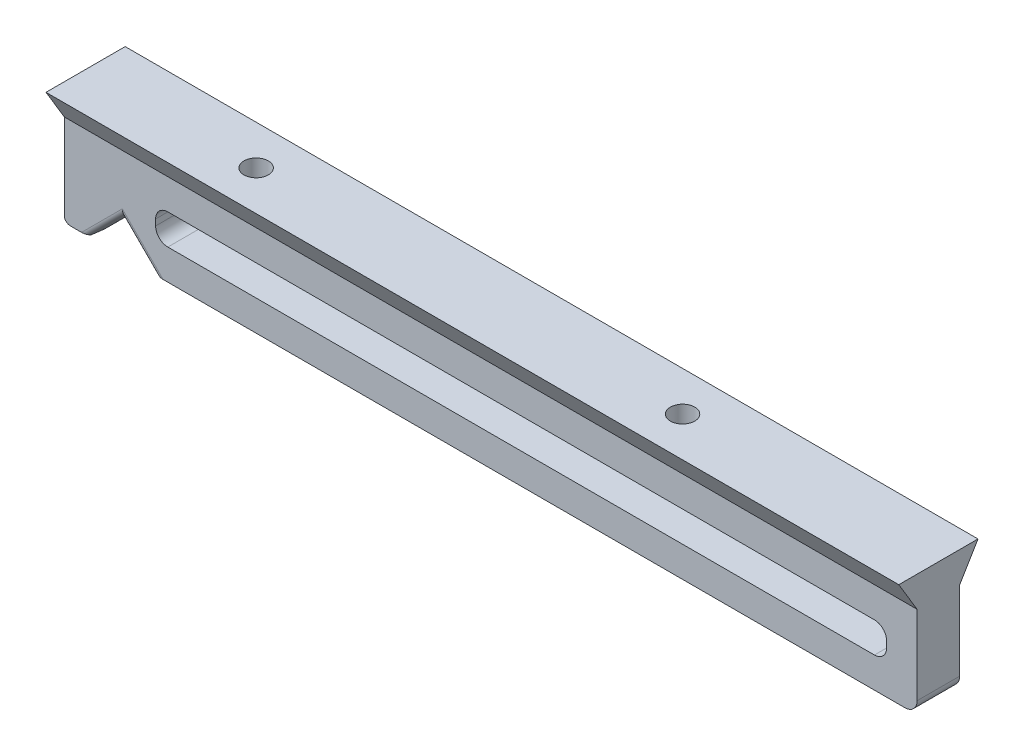
SolidWorks part; units mm, degrees
ref_plane "Front Plane" through (0, 0, 0) normal (0, 0, 1) x (1, 0, 0)
ref_plane "Top Plane" through (0, 0, 0) normal (0, 1, 0) x (1, 0, 0)
ref_plane "Right Plane" through (0, 0, 0) normal (1, 0, 0) x (0, 0, -1)
sketch "Sketch1" plane through (0, 0, 0) normal (0, 1, 0) x (1, 0, 0)
  line L1 (-70, 3.5) -> (70, 3.5)
  line L2 (-70, 3.5) -> (-70, -3.5)
  line L3 (-70, -3.5) -> (70, -3.5)
  line L4 (70, 3.5) -> (70, -3.5)
  line L5 (-70, 3.5) -> (70, -3.5) construction
  line L6 (-70, -3.5) -> (70, 3.5) construction
  point P0 (0, 0)
  dimension "D1" = 140
  dimension "D2" = 7
extrude "Boss-Extrude1" add sketch "Sketch1" along normal blind 20
sketch "Sketch2" plane through (0, 20, 0) normal (0, 1, 0) x (1, 0, 0)
  circle A0 centre (-42, 0) radius 2
  circle A1 centre (28, 0) radius 2
  dimension "D2" = 4
  dimension "D3" = 4
  dimension "D1" = 70
  dimension "D4" = 28
extrude "Cut-Extrude1" cut sketch "Sketch2" against normal blind 10
sketch "Sketch4" plane through (-70, 0, 0) normal (-1, 0, 0) x (0, 0, 1)
  line L0 (-3.5, 15) -> (-3.5, 20)
  line L1 (-3.5, 20) -> (-3.5, 0) construction
  line L2 (-3.5, 20) -> (-6.5, 20)
  line L3 (-6.5, 20) -> (-3.5, 15)
  line L4 (3.5, 20) -> (6.5, 20)
  line L5 (6.5, 20) -> (3.5, 15)
  line L6 (3.5, 20) -> (3.5, 0) construction
  line L7 (3.5, 20) -> (3.5, 15)
  dimension "D1" = 3
  dimension "D2" = 3
  dimension "D3" = 5
  dimension "D4" = 5
extrude "Boss-Extrude2" add sketch "Sketch4" against normal up to surface (140 mm away) up to face at (70, 10, 0)
ref_plane "Plane1" through (-35, 35, 0) normal (-0.7071, 0.7071, 0) x (0.7071, 0.7071, 0)
sketch "Sketch5" plane through (-35, 35, 0) normal (-0.7071, 0.7071, 0) x (0.7071, 0.7071, 0)
  line L0 (-35.3553, 6.5) -> (-35.3553, -6.5) construction
  circle A0 centre (-42.3553, 0) radius 2
  dimension "D2" = 4
  dimension "D1" = 7
extrude "Cut-Extrude2" cut sketch "Sketch5" against normal through all both and the other way through all
sketch "Sketch6" plane through (-35, 35, 0) normal (-0.7071, 0.7071, 0) x (0.7071, 0.7071, 0)
  circle A0 centre (-42.3553, 0) radius 4
  dimension "D1" = 8
extrude "Cut-Extrude3" cut sketch "Sketch6" against normal blind 10 from offset 3 offset against normal yes
sketch "Sketch7" plane through (0, 0, -3.5) normal (0, 0, -1) x (-1, 0, 0)
  line L0 (64.1977, 1.5596) -> (67.7948, -1.4912)
  line L1 (67.7948, -1.4912) -> (62.6381, 0)
  line L2 (62.6381, 0) -> (64.1977, 1.5596)
extrude "Cut-Extrude4" cut sketch "Sketch7" against normal blind 10
fillet "Fillet1" radius 1 5 edges at (-70, 0, 0) (-62.8284, 2.9289, -3.5) (-62.8284, 2.9289, 3.5) (-59.31, 2.1491, -3.5) (-59.31, 2.1491, 3.5)
sketch "Sketch8" plane through (0, 0, -3.5) normal (0, 0, -1) x (-1, 0, 0)
  line L0 (-70, 15) -> (-70, 0) construction
  line L1 (-65, 10) -> (55, 10)
  line L2 (-65, 10) -> (-65, 5)
  line L3 (-65, 5) -> (55, 5)
  line L4 (55, 10) -> (55, 5)
  line L5 (-70, 15) -> (70, 15) construction
  line L6 (-70, 0) -> (53.7758, 0) construction
  line L7 (70, 15) -> (70, 1) construction
  dimension "D1" = 5
  dimension "D2" = 5
  dimension "D3" = 5
  dimension "D4" = 15
extrude "Cut-Extrude5" cut sketch "Sketch8" against normal blind 10
fillet "Fillet2" radius 2 4 edges at (65, 10, 0) (65, 5, 0) (-55, 5, 0) (-55, 10, 0)
fillet "Fillet3" radius 2 1 edges at (70, 0, 0)
